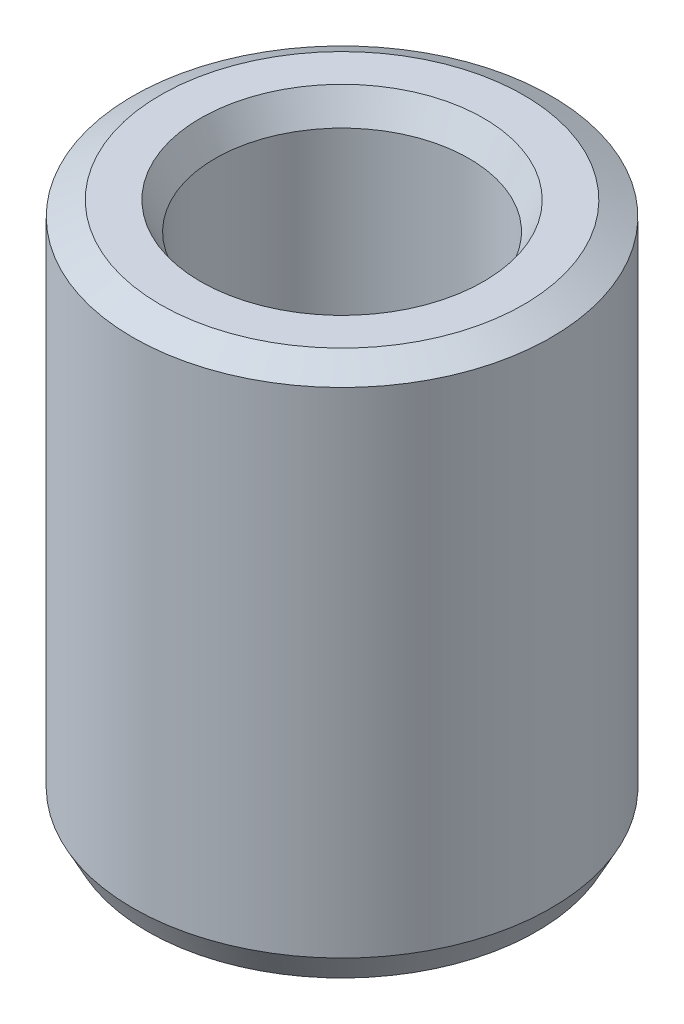
SolidWorks part; units mm, degrees
ref_plane "Front Plane" through (0, 0, 0) normal (0, 0, 1) x (1, 0, 0)
ref_plane "Top Plane" through (0, 0, 0) normal (0, 1, 0) x (1, 0, 0)
ref_plane "Right Plane" through (0, 0, 0) normal (1, 0, 0) x (0, 0, -1)
sketch "Sketch1" plane through (0, 0, 0) normal (0, 1, 0) x (1, 0, 0)
  circle A0 centre (0, 0) radius 50
  dimension "SLEEVE_OD" = 100
extrude "Boss-Extrude1" add sketch "Sketch1" along normal blind 128.2016
sketch "Sketch2" plane through (0, 0, 0) normal (0, 1, 0) x (1, 0, 0)
  circle A0 centre (0, 0) radius 30.3399
  dimension "BORE_D" = 60.6797
extrude "Cut-Extrude1" cut sketch "Sketch2" along normal through all
chamfer "Chamfer1" distance 3.4938 angle 62.079 4 edges at (0, 128.2016, 30.3399) (0, 0, 30.3399) (0, 0, 50) (0, 128.2016, 50) first distance on face at (0, 128.2016, 30.3399) first distance on face at (0, 0, 30.3399) first distance on face at (0, 128.2016, 50)
